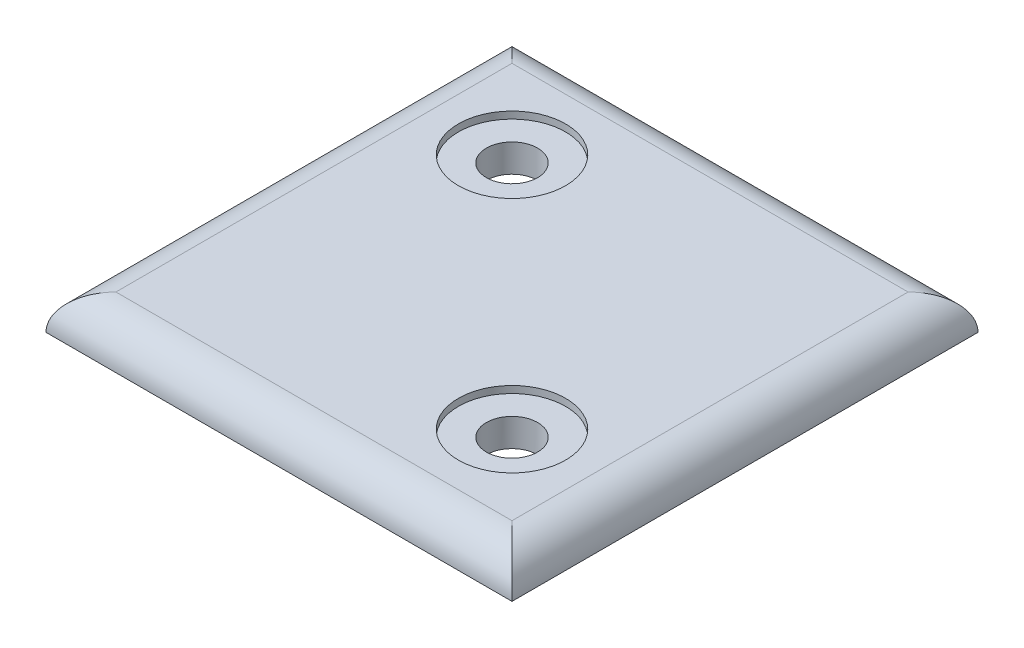
SolidWorks part; units mm, degrees
ref_plane "Front Plane" through (0, 0, 0) normal (0, 0, 1) x (1, 0, 0)
ref_plane "Top Plane" through (0, 0, 0) normal (0, 1, 0) x (1, 0, 0)
ref_plane "Right Plane" through (0, 0, 0) normal (1, 0, 0) x (0, 0, -1)
sketch "Sketch1" plane through (0, 0, 0) normal (0, 1, 0) x (1, 0, 0)
  line L1 (-20, 20) -> (20, 20)
  line L2 (-20, 20) -> (-20, -20)
  line L3 (-20, -20) -> (20, -20)
  line L4 (20, 20) -> (20, -20)
  line L5 (-20, 20) -> (20, -20) construction
  line L6 (-20, -20) -> (20, 20) construction
  point P0 (0, 0)
  dimension "D1" = 40
extrude "Boss-Extrude1" add sketch "Sketch1" along normal blind 3
sketch "Sketch2" plane through (0, 3, 0) normal (0, 1, 0) x (1, 0, 0)
  line L0 (-20, 20) -> (20, -20) construction
  line L1 (20, 20) -> (-20, 20) construction
  line L2 (-20, 20) -> (-20, -20) construction
  line L3 (20, 20) -> (-20, -20) construction
  circle A0 centre (-10.2, 10.2) radius 2.2
  circle A1 centre (10.2, -10.2) radius 2.2
  dimension "D3" = 4.4
  dimension "D1" = 9.8
  dimension "D2" = 9.8
extrude "Cut-Extrude1" cut sketch "Sketch2" against normal through all
sketch "Sketch3" plane through (0, 3, 0) normal (0, 1, 0) x (1, 0, 0)
  circle A0 centre (-10.2, 10.2) radius 4.6
  circle A1 centre (10.2, -10.2) radius 4.6
  dimension "D1" = 9.2
extrude "Cut-Extrude2" cut sketch "Sketch3" against normal blind 0.6
fillet "Fillet1" radius 3 4 edges at (20, 3, 0) (-20, 3, 0) (0, 3, 20) (0, 3, -20)
